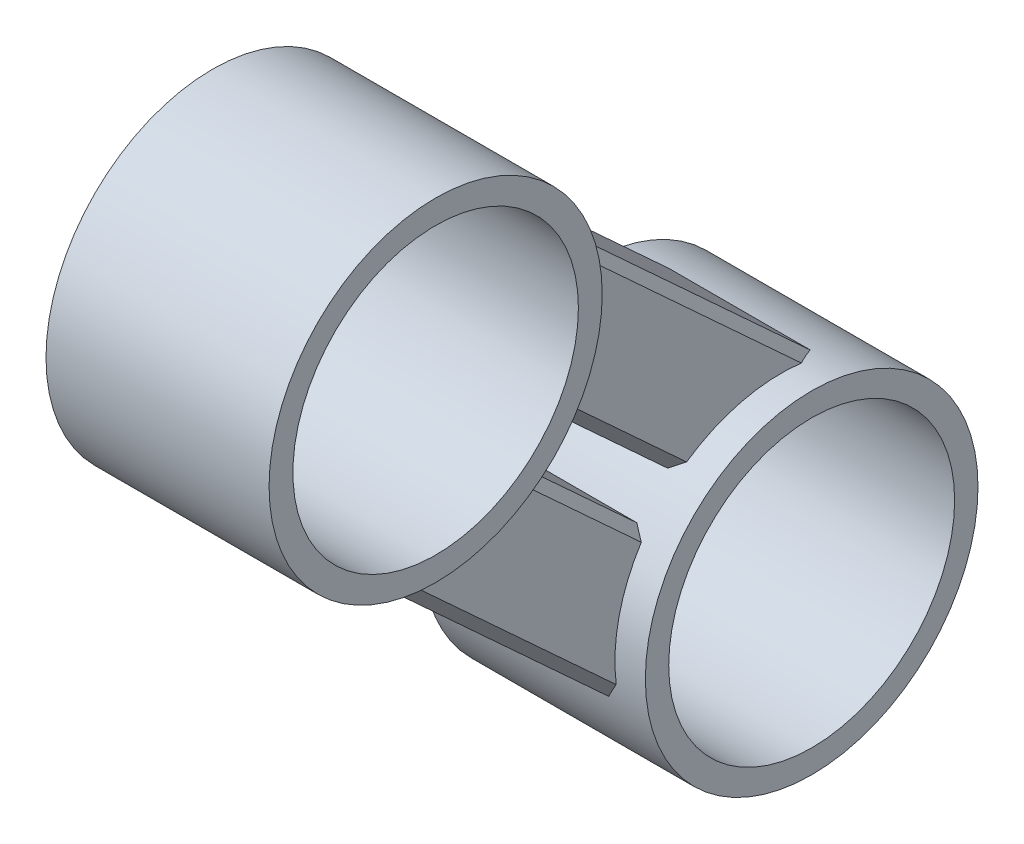
SolidWorks part; units mm, degrees
ref_plane "Front Plane" through (0, 0, 0) normal (0, 0, 1) x (1, 0, 0)
ref_plane "Top Plane" through (0, 0, 0) normal (0, 1, 0) x (1, 0, 0)
ref_plane "Right Plane" through (0, 0, 0) normal (1, 0, 0) x (0, 0, -1)
sketch "Sketch1" plane through (0, 0, 0) normal (1, 0, 0) x (0, 0, -1)
  line L0 (36.6961, 520.112) -> (94.9292, 466.5782)
  line L1 (94.9292, 466.5782) -> (79.6, 451.2488)
  line L2 (79.6, 451.2488) -> (21.367, 504.7826)
  line L3 (21.367, 504.7826) -> (36.6961, 520.112)
  line L4 (15.6779, 499.0937) -> (73.9112, 445.5597)
  line L5 (73.9112, 445.5597) -> (58.5818, 430.2305)
  line L6 (58.5818, 430.2305) -> (0.3487, 483.7646)
  line L7 (0.3487, 483.7646) -> (15.6779, 499.0937)
  circle A0 centre (18.5694, 502.5418) radius 30.2243
  circle A1 centre (86.7984, 438.1663) radius 30.1778
  point P12 (112.7763, 422.8089)
  point P13 (-7.5982, 517.6667)
extrude "Boss-Extrude2" add sketch "Sketch1" along normal blind 14.7132 and the other way blind 14.7132 contours A1 L4 A0 L6 | A1 L0 A0 L2 | L6 A0 L4 L7 | L2 A0 L0 L3 | L0 A0 L6 L7 L4 L2 L3 | L2 A1 L4 L5 L6 L0 L1 | L0 A1 L2 L1 | L4 A1 L6 L5 region at (0, 508.1886, -13.0371) region at (0, 503.2084, -37.6141) region at (0, 481.882, -63.9245) region at (0, 435.3027, -89.6432) region at (0, 461.5837, -81.1338) region at (0, 458.9863, -41.6888) region at (0, 483.3551, -18.1635) region at (0, 443.5873, -63.3437)
extrude "Boss-Extrude3" add sketch "Sketch1<3>" along normal blind 20.2366 and the other way blind 20.2366 contours L0 A0 L6 L7 L4 L2 L3 | L2 A1 L4 L5 L6 L0 L1 | L4 A1 L6 L5 | L0 A1 L2 L1 | L2 A0 L0 L3 | L6 A0 L4 L7 region at (0, 508.1886, -13.0371) region at (0, 503.2084, -37.6141) region at (0, 435.3027, -89.6432) region at (0, 461.5837, -81.1338) region at (0, 483.3551, -18.1635) region at (0, 443.5873, -63.3437)
sketch "Sketch1<3>" plane through (0, 0, 0) normal (1, 0, 0) x (0, 0, -1) same geometry as "Sketch1"
sketch "Sketch2" plane through (20.2366, 0, 0) normal (1, 0, 0) x (0, 0, -1)
  circle A0 centre (18.5694, 502.5418) radius 25.9022
  circle A1 centre (86.7984, 438.1663) radius 25.9393
  point P6 (44.4716, 502.5418)
  point P7 (109.2304, 451.1914)
extrude "Cut-Extrude1" cut sketch "Sketch2" against normal through all
chamfer "Chamfer1" distance 1.8946 8 edges at (-14.7132, 452.1716, -34.7148) (-14.7132, 467.53, -50.0124) (-14.7132, 473.3371, -55.5728) (-14.7132, 488.6457, -70.9246) (14.7132, 452.1716, -34.7148) (14.7132, 467.53, -50.0124) (14.7132, 473.3371, -55.5728) (14.7132, 488.6457, -70.9246)
